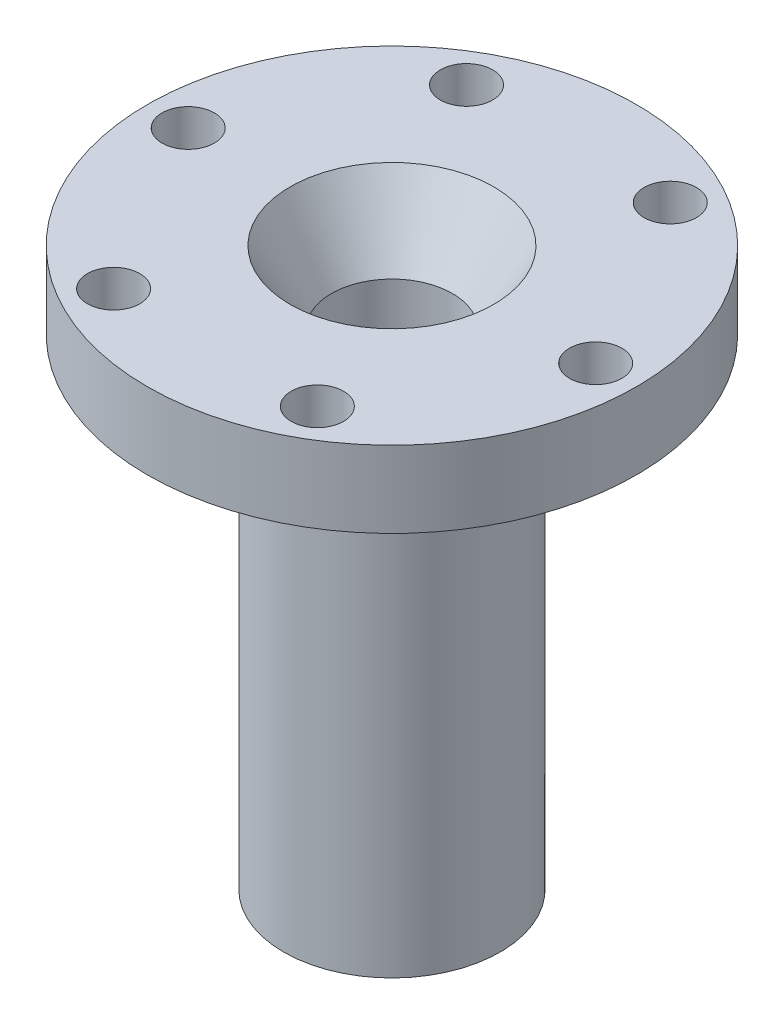
SolidWorks part; units mm, degrees
material "AISI Type 316L stainless steel"
ref_plane "Front Plane" through (0, 0, 0) normal (0, 0, 1) x (1, 0, 0)
ref_plane "Top Plane" through (0, 0, 0) normal (0, 1, 0) x (1, 0, 0)
ref_plane "Right Plane" through (0, 0, 0) normal (1, 0, 0) x (0, 0, -1)
sketch "Sketch1" plane through (0, 0, 0) normal (0, 0, 1) x (1, 0, 0)
  line L0 (0, 0) -> (0, -29.8554) construction
  line L1 (7.5, -69.525) -> (7.5, -9.0067)
  line L2 (7.5, -9.0067) -> (12.7, 0)
  line L3 (12.7, 0) -> (30.48, 0)
  line L4 (30.48, 0) -> (30.48, -9.525)
  line L5 (30.48, -9.525) -> (13.5, -9.525)
  line L6 (13.5, -9.525) -> (13.5, -69.525)
  line L7 (13.5, -69.525) -> (7.5, -69.525)
  dimension "D1" = 27
  dimension "D2" = 15
  dimension "D3" = 60
  dimension "D4" = 30
  dimension "D5" = 25.4
  dimension "D6" = 60.96
  dimension "D7" = 9.525
revolve "Revolve1" add sketch "Sketch1" angle 360 about L0
hole_wizard "1/4 Clearance Hole1" positions "Sketch3" profile "Sketch4" hole size "1/4" standard "ANSI Inch" end condition through all
sketch "Sketch3" plane through (0, 0, 0) normal (0, 1, 0) x (1, 0, 0)
  line L0 (25.4, 0) -> (0, 0) construction
  point P0 (25.4, 0)
  dimension "D1" = 25.4
sketch "Sketch4" plane through (25.4, 0, 0) normal (1, 0, 0) x (0, 0, 1)
  line L0 (0, 0) -> (0, 69.525)
  line L1 (0, 69.525) -> (3.2639, 69.525)
  line L2 (3.2639, 69.525) -> (3.2639, 0)
  line L5 (3.2639, 0) -> (0, 0)
  line L11 (0, -6.35) -> (0, 107.95) construction
  dimension "Thru Hole Dia." = 6.5278
  dimension "Thru Hole Depth" = 69.525
pattern_circular "CirPattern1" count 6 over 360 about axis through (0, 0, 0) along (0, 1, 0) of "1/4 Clearance Hole1" reverse direction yes
sketch "Sketch5" plane through (0, 0, 0) normal (0, 1, 0) x (1, 0, 0)
  circle A0 centre (0, 0) radius 25.4
  dimension "D1" = 50.8
chamfer "Chamfer1" distance 2.032 angle 22 1 edges at (0, -69.525, 7.5) first distance on face at (0, -69.525, 13.5)
fillet "Fillet1" radius 0.7937 1 edges at (0, -68.704, 7.5)
chamfer "Chamfer2" distance 3.175 angle 45 1 edges at (0, -9.525, 13.5)
sketch "Sketch6" plane through (0, -69.525, 0) normal (0, -1, 0) x (1, 0, 0)
  circle A0 centre (0, 0) radius 7.5 construction
  circle A1 centre (0, 0) radius 7.5
  circle A2 centre (0, 0) radius 2.73
  circle A3 centre (0, 0) radius 3.73
  circle A5 centre (0, 0) radius 9.532 construction
  circle A6 centre (0, 0) radius 9.532
  circle M6 centre (0, 0) radius 9.532
  circle M7 centre (0, 0) radius 13.5
  dimension "D1" = 5.46
  dimension "D2" = 1
extrude "Boss-Extrude1" add sketch "Sketch6" against normal blind 10 from offset 6.35 contours M7 M6 | A3 A2 region at (-3.6245, -69.525, 0) region at (-13.1182, -69.525, 0) offset against normal yes
sketch "Sketch7" plane through (0, -63.175, 0) normal (0, -1, 0) x (1, 0, 0)
  line L0 (0, 0) -> (0, 2.73) construction
  line L1 (-0.5, 8.532) -> (0.5, 8.532)
  line L2 (-0.5, 8.532) -> (-0.5, 2.73)
  line L3 (-0.5, 2.73) -> (0.5, 2.73)
  line L4 (0.5, 8.532) -> (0.5, 2.73)
  line L5 (0, 9.532) -> (0, 8.532) construction
  circle A1 centre (0, 0) radius 2.73 construction
  circle A2 centre (0, 0) radius 9.532 construction
  dimension "D1" = 1
  dimension "D2" = 1
extrude "Boss-Extrude2" add sketch "Sketch7" against normal up to surface (10 mm away) up to face at (0, -53.175, -2.73)
fillet "Fillet2" radius 1.651 4 edges at (-0.5, -58.175, 3.6963) (0.5, -58.175, 3.6963) (-0.5, -58.175, 7.4833) (0.5, -58.175, 7.4833)
pattern_circular "CirPattern2" count 3 over 360 about axis through (0, 0, 0) along (0, 1, 0) of "Boss-Extrude2", "Fillet2"
hole_wizard "19/32 (0.59375) Diameter Hole1" positions "Sketch8" profile "Sketch10" hole size "19/32" standard "ANSI Inch"
sketch "Sketch8" plane through (0, 0, 0) normal (0, 1, 0) x (1, 0, 0)
  point P0 (0, 0)
sketch "Sketch10" plane through (0, 0, 0) normal (1, 0, 0) x (0, 0, 1)
  line L0 (0, 0) -> (0, 61.6809)
  line L1 (0, 61.6809) -> (7.5406, 57.15)
  line L2 (7.5406, 57.15) -> (7.5406, 0)
  line L5 (7.5406, 0) -> (0, 0)
  line L10 (0, 61.6809) -> (-7.5406, 57.15) construction
  line L11 (0, -6.35) -> (0, 107.95) construction
  dimension "Hole Dia." = 15.0812
  dimension "Hole Depth" = 57.15
  dimension "Drill Angle" = 118
